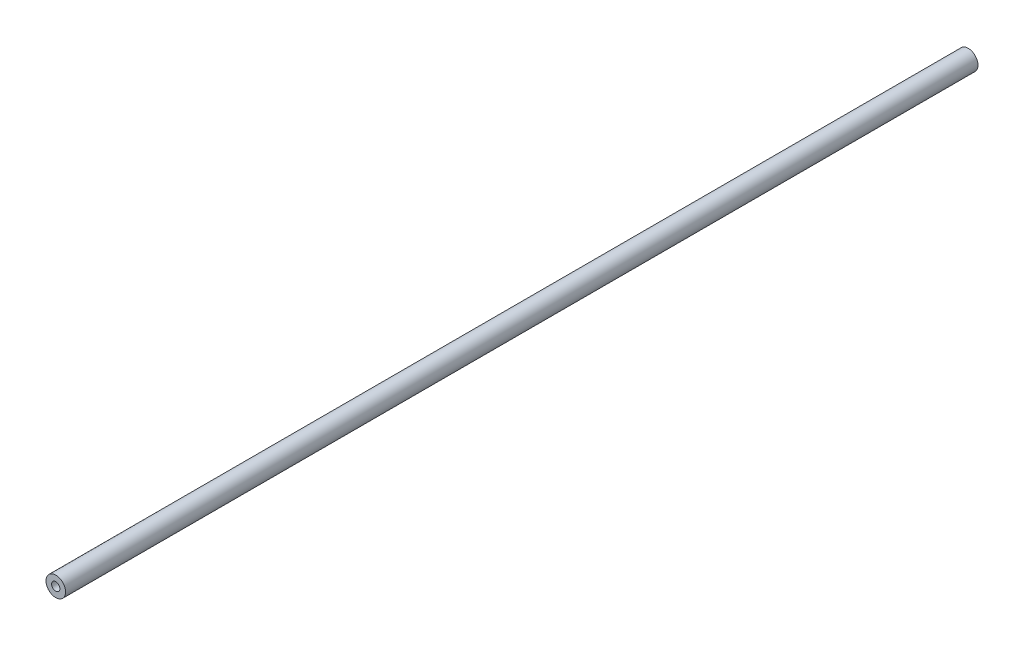
SolidWorks part; units mm, degrees
ref_plane "Front Plane" through (0, 0, 0) normal (0, 0, 1) x (1, 0, 0)
ref_plane "Top Plane" through (0, 0, 0) normal (0, 1, 0) x (1, 0, 0)
ref_plane "Right Plane" through (0, 0, 0) normal (1, 0, 0) x (0, 0, -1)
sketch "Sketch1" plane through (0, 0, 0) normal (0, 0, 1) x (1, 0, 0)
  circle A1 centre (0, 0) radius 4.7625
  dimension "D2" = 9.525
extrude "Boss-Extrude1" add sketch "Sketch1" along normal blind 444.5 contours A1 region at (0, 0, 0)
hole_wizard "#10-32 Tapped Hole1" positions "3DSketch1" profile "Sketch2" tap size "#10-32" standard "ANSI Inch"
sketch3d "3DSketch1"
  line L0 (0, 0, 444.5) -> (0, 0, 0) construction
  circle A3 centre (0, 0, 0) radius 4.7625 construction
  point P0 (0, 0, 444.5)
  point P7 (0, 0, 0)
  point P10 (0, 0, 0)
  point P12 (0, 0, 0)
  point P14 (0, 0, 0)
  point P17 (0, 0, 0)
  point P18 (-12.0153, -11.3492, 0)
  point P31 (-0.9995, -1.7312, 0)
  point P35 (0, 0, 4.7625)
sketch "Sketch2" plane through (0, 0, 444.5) normal (1, 0, 0) x (0, -1, 0)
  line L0 (0, 0) -> (0, 16.2908)
  line L1 (0, 16.2908) -> (2.0193, 15.0774)
  line L2 (2.0193, 15.0774) -> (2.0193, 0)
  line L5 (2.0193, 0) -> (0, 0)
  line L10 (0, 16.2908) -> (-2.0193, 15.0774) construction
  line L11 (0, -6.35) -> (0, 107.95) construction
  dimension "Tap Drill Dia." = 4.0386
  dimension "Tap Drill Depth" = 15.0774
  dimension "Drill Angle" = 118
cosmetic thread "Hole Thread4"
cosmetic thread "Hole Thread5"
